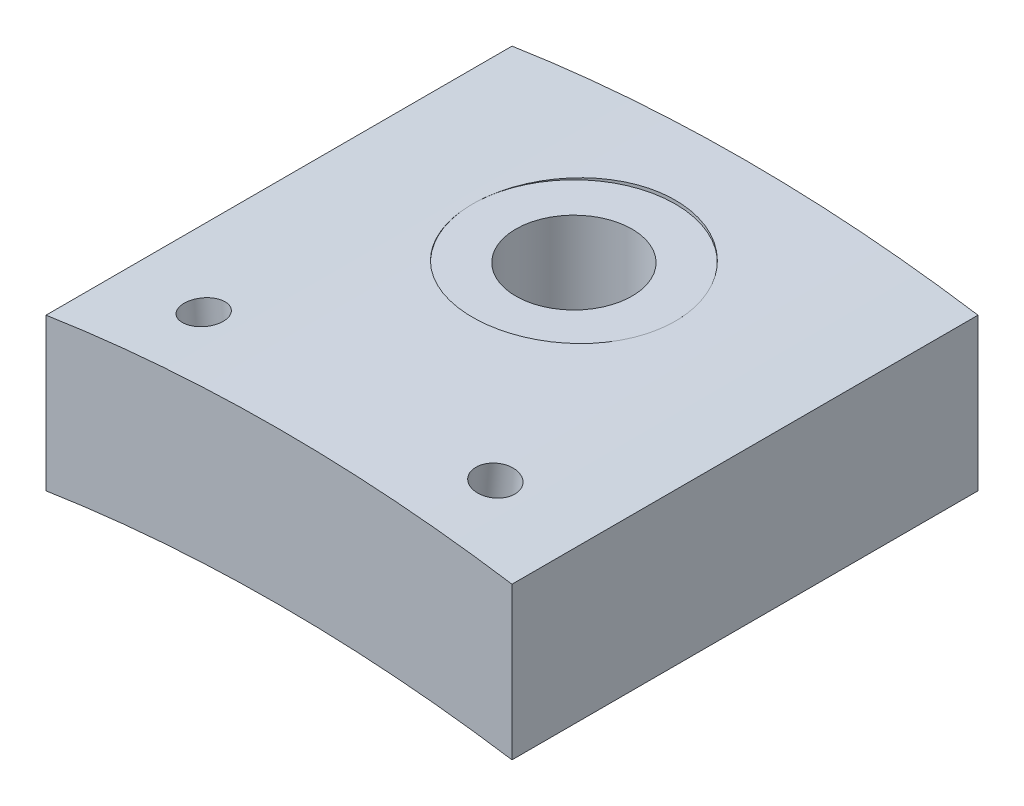
SolidWorks part; units mm, degrees
ref_plane "Front Plane" through (0, 0, 0) normal (0, 0, 1) x (1, 0, 0)
ref_plane "Top Plane" through (0, 0, 0) normal (0, 1, 0) x (1, 0, 0)
ref_plane "Right Plane" through (0, 0, 0) normal (1, 0, 0) x (0, 0, -1)
sketch "Sketch1" plane through (0, 0, 0) normal (0, 0, 1) x (1, 0, 0)
  line L1 (0, 0) -> (-35, 0)
  line L2 (0, 0) -> (0, -19)
  line L3 (0, -19) -> (-35, -19)
  line L4 (-35, 0) -> (-35, -19)
  arc A0 (-35, -19) -> (0, -19) centre (-17.5, -132.0809) cw
  dimension "D1" = 35
  dimension "D3" = 114.427
  dimension "D2" = 19
extrude "Boss-Extrude1" add sketch "Sketch1" along normal blind 35 contours L4 A0 L2 L1 region at (-17.5, -9.0552, 0)
ref_plane "Plane2" through (0, -17.6539, 0) normal (0, -1, 0) x (1, 0, 0)
ref_plane "Plane3" through (-1.6278, -18.6054, 0) normal (-0.0872, -0.9962, 0) x (0.9962, -0.0872, 0)
ref_plane "Plane4" through (1.3619, -15.5666, 0) normal (0.0872, -0.9962, 0) x (0.9962, 0.0872, 0)
sketch "Sketch3" plane through (0, 0, 35) normal (0, 0, 1) x (1, 0, 0)
  line L0 (-17.5, -131.9524) -> (-17.5, 0) construction
  line L1 (0, 0) -> (-35, 0) construction
  line L2 (-17.5, -131.9524) -> (-5.9557, 0) construction
  line L3 (-17.5, -131.9524) -> (-29.0443, 0) construction
  circle A0 centre (-17.5, -131.9524) radius 114.3
  dimension "D1" = 228.6
  dimension "D2" = 5
  dimension "D3" = 5
sketch "Sketch6" plane through (-1.6278, -18.6054, 0) normal (-0.0872, -0.9962, 0) x (0.9962, -0.0872, 0)
  line L0 (-5.933, 35) -> (-5.933, 0) construction
  line L1 (108.367, 35) -> (-120.233, 35) construction
  line L2 (1.656, 0) -> (-33.2109, 0) construction
  circle A0 centre (-5.933, 29.7028) radius 1.4732
  dimension "D1" = 2.9464
  dimension "D2" = 29.7028
extrude "Cut-Extrude4" cut sketch "Sketch6" against normal through all and the other way through all
sketch "Sketch7" plane through (1.3619, -15.5666, 0) normal (0.0872, -0.9962, 0) x (0.9962, 0.0872, 0)
  line L0 (-28.9338, 35) -> (-28.9338, 0) construction
  line L1 (85.3662, 35) -> (-143.2338, 35) construction
  line L2 (-1.656, 0) -> (-36.5228, 0) construction
  circle A0 centre (-28.9338, 29.7028) radius 1.4732
  dimension "D1" = 2.9464
  dimension "D2" = 29.7028
extrude "Cut-Extrude5" cut sketch "Sketch7" against normal through all and the other way through all
sketch "Sketch8" plane through (0, 0, 0) normal (0, 0, -1) x (-1, 0, 0)
  line L0 (0, -7.572) -> (35, -7.572) construction
  line L1 (17.5, -17.6539) -> (17.5, -6.2244) construction
  line L3 (35, -19) -> (35, 0)
  line L4 (35, 0) -> (0, 0)
  line L5 (0, 0) -> (0, -19)
  line L6 (35, -19) -> (35, 0)
  line L7 (35, 0) -> (0, 0)
  line L8 (0, 0) -> (0, -19)
  arc A0 (0, -7.572) -> (35, -7.572) centre (17.5, -120.5244) cw
  arc A1 (35, -19) -> (0, -19) centre (17.5, -132.0809) ccw
  arc A2 (35, -19) -> (0, -19) centre (17.5, -132.0809) ccw
  line M6 (35, 0) -> (0, 0)
  line M7 (0, 0) -> (0, -19)
  dimension "D2" = 11.428
  dimension "D3" = 114.3
  dimension "D1" = 0
extrude "Cut-Extrude6" cut sketch "Sketch8" against normal through all contours A0 L6 M7 M6 region at (-17.5, -3.3483, 0)
ref_plane "Plane5" through (-17.5, -6.2244, 0) normal (0, 1, 0) x (-1, 0, 0)
sketch "Sketch9" plane through (-17.5, -6.2244, 0) normal (0, 1, 0) x (-1, 0, 0)
  line L0 (0, 0) -> (0, 35) construction
  line L1 (-17.5, 0) -> (17.5, 0) construction
  line L2 (17.5, 35) -> (-17.5, 35) construction
  circle A0 centre (0, 12.85) radius 7.62
  circle A1 centre (0, 12.85) radius 3
  circle A2 centre (0, 12.85) radius 4.3656
  dimension "D1" = 12.85
  dimension "D2" = 15.24
  dimension "D3" = 6
  dimension "D4" = 8.7312
extrude "Cut-Extrude7" cut sketch "Sketch9" against normal through all contours L0 A1 | A1 L0 region at (-16.2268, -6.2244, 12.85) region at (-18.7732, -6.2244, 12.85)
extrude "Cut-Extrude8" cut sketch "Sketch9<3>" against normal blind 8.255 contours L0 A2 A1 | A2 L0 A1 region at (-13.232, -6.2244, 12.85) region at (-17.5976, -6.2244, 9.1672)
sketch "Sketch9<3>" plane through (-17.5, -6.2244, 0) normal (0, 1, 0) x (-1, 0, 0) same geometry as "Sketch9"
extrude "Cut-Extrude9" cut sketch "Sketch9<4>" against normal blind 0.254 contours A0 L0 A2 | L0 A0 A2 region at (-10.0504, -6.2244, 12.85) region at (-17.6704, -6.2244, 6.8572)
sketch "Sketch9<4>" plane through (-17.5, -6.2244, 0) normal (0, 1, 0) x (-1, 0, 0) same geometry as "Sketch9"
